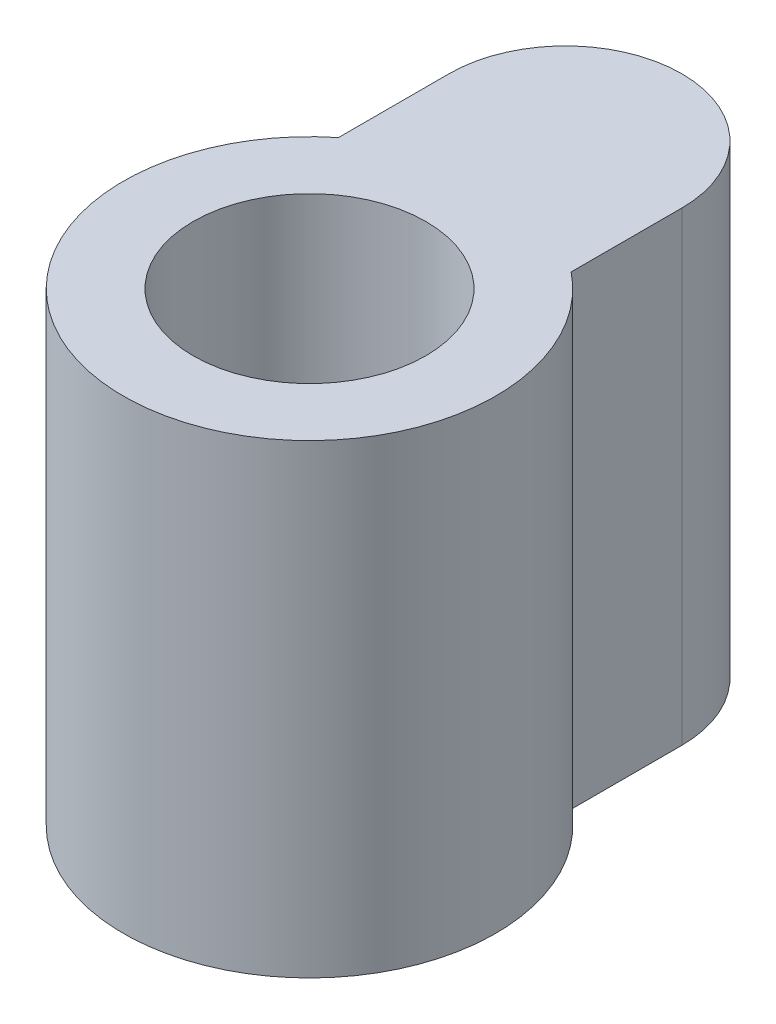
SolidWorks part; units mm, degrees
ref_plane "Alzado" through (0, 0, 0) normal (0, 0, 1) x (1, 0, 0)
ref_plane "Planta" through (0, 0, 0) normal (0, 1, 0) x (1, 0, 0)
ref_plane "Vista lateral" through (0, 0, 0) normal (1, 0, 0) x (0, 0, -1)
sketch "Croquis1" plane through (0, 0, 0) normal (0, 1, 0) x (1, 0, 0)
  line L6 (-2.5, 8) -> (2.5, 8)
  line L7 (-2.5, 8) -> (-2.5, 3.1225)
  line L9 (2.5, 8) -> (2.5, 3.1225)
  circle A0 centre (0, 0) radius 2.5
  arc A1 (-2.5, 3.1225) -> (2.5, 3.1225) centre (0, 0) ccw
  dimension "D1" = 5
  dimension "D2" = 5
  dimension "D5" = 4.8775
extrude "Saliente-Extruir1" add sketch "Croquis1" along normal blind 10
fillet "Redondeo1" 2 edges at (-2.5, 5, -8) (2.5, 5, -8) type full round first side face at (-2.5, 5, -5.5612) second side face at (2.5, 5, -5.5612) middle face at (0, 5, -8)
